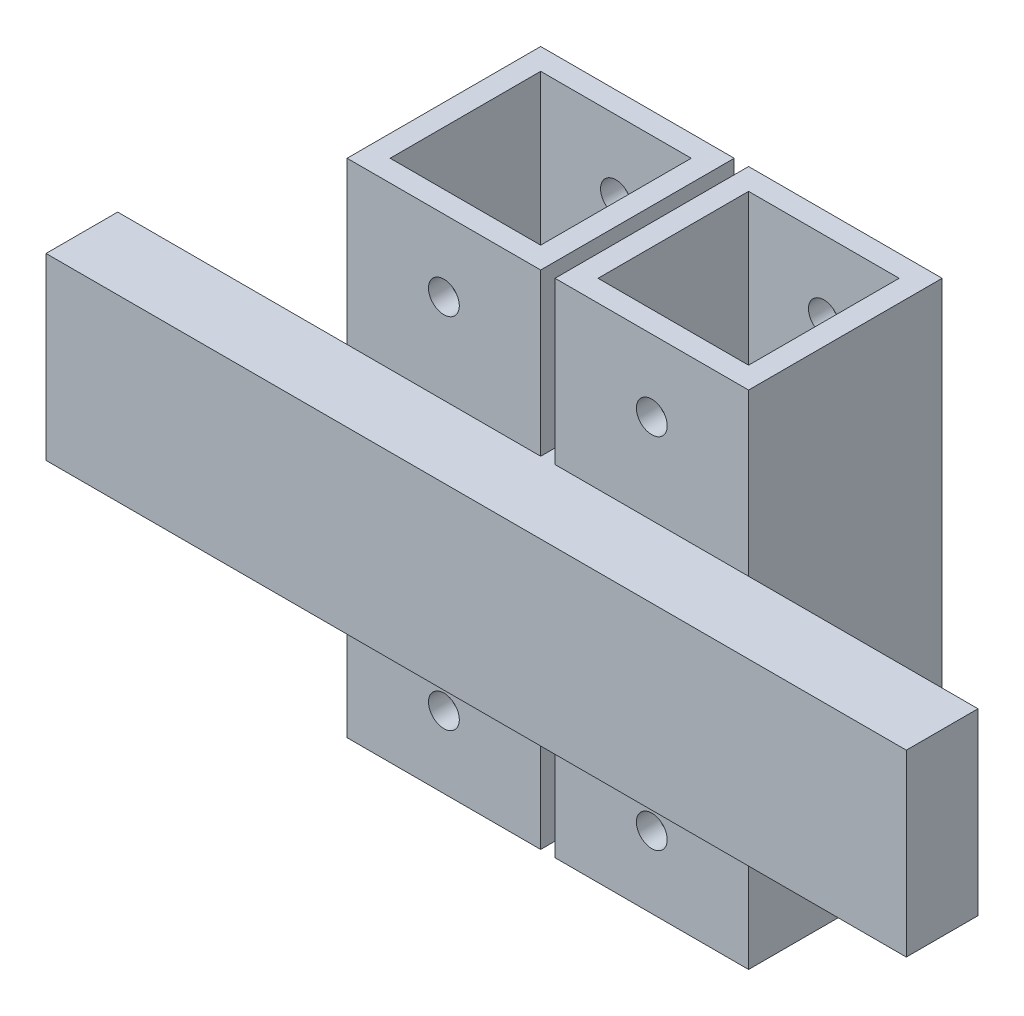
SolidWorks part; units mm, degrees
ref_plane "Front Plane" through (0, 0, 0) normal (0, 0, 1) x (1, 0, 0)
ref_plane "Top Plane" through (0, 0, 0) normal (0, 1, 0) x (1, 0, 0)
ref_plane "Right Plane" through (0, 0, 0) normal (1, 0, 0) x (0, 0, -1)
sketch "Sketch1" plane through (0, 0, 0) normal (0, 1, 0) x (1, 0, 0)
  line L1 (0, 0) -> (27, 0)
  line L2 (0, 0) -> (0, 27)
  line L3 (0, 27) -> (27, 27)
  line L4 (27, 0) -> (27, 27)
  line L5 (3, 24) -> (24, 24)
  line L6 (3, 24) -> (3, 3)
  line L7 (3, 3) -> (24, 3)
  line L8 (24, 24) -> (24, 3)
  line L9 (-29, 27) -> (-2, 27)
  line L10 (-29, 27) -> (-29, 0)
  line L11 (-29, 0) -> (-2, 0)
  line L12 (-2, 27) -> (-2, 0)
  line L13 (-5, 24) -> (-26, 24)
  line L14 (-5, 24) -> (-5, 3)
  line L15 (-5, 3) -> (-26, 3)
  line L16 (-26, 24) -> (-26, 3)
  line L17 (-25.5, 23.5) -> (-5.5, 23.5) construction
  line L18 (-25.5, 23.5) -> (-25.5, 3.5) construction
  line L19 (-25.5, 3.5) -> (-5.5, 3.5) construction
  line L20 (-5.5, 23.5) -> (-5.5, 3.5) construction
  line L21 (3.5, 23.5) -> (23.5, 23.5) construction
  line L22 (3.5, 23.5) -> (3.5, 3.5) construction
  line L23 (3.5, 3.5) -> (23.5, 3.5) construction
  line L24 (23.5, 23.5) -> (23.5, 3.5) construction
  point P25 (2.5347, 20.3062)
  point P26 (-27.2369, 24.3411)
  point P27 (-25.9138, 2.1783)
  point P28 (4.096, 3.2633)
  dimension "D1" = 9
  dimension "D2" = 0.5
  dimension "D3" = 3
  dimension "D4" = 3
  dimension "D5" = 3
  dimension "D6" = 3
  dimension "D7" = 3
  dimension "D8" = 20
  dimension "D9" = 0.5
  dimension "D10" = 0.5
  dimension "D11" = 0.5
extrude "Boss-Extrude1" add sketch "Sketch1" along normal blind 70
sketch "Sketch2" plane through (0, 0, 0) normal (0, 0, 1) x (1, 0, 0)
  line L0 (-29, 70) -> (-29, 0) construction
  line L1 (-61, 47.5) -> (59, 47.5)
  line L2 (-61, 47.5) -> (-61, 22.5)
  line L3 (-61, 22.5) -> (59, 22.5)
  line L4 (59, 47.5) -> (59, 22.5)
  line L5 (-51, 42.5) -> (49, 42.5) construction
  line L6 (-51, 42.5) -> (-51, 27.5) construction
  line L7 (-51, 27.5) -> (49, 27.5) construction
  line L8 (49, 42.5) -> (49, 27.5) construction
  point P8 (-1, 27.5)
  point P9 (-1, 22.5)
  point P10 (-61, 35)
  point P11 (-51, 35)
  point P14 (-29, 35)
  dimension "D1" = 100
  dimension "D2" = 10
  dimension "D3" = 22
  dimension "D4" = 25
  dimension "D5" = 5
extrude "Boss-Extrude2" add sketch "Sketch2" along normal blind 10
sketch "Sketch3" plane through (0, 0, -27) normal (0, 0, -1) x (-1, 0, 0)
  line L1 (0, 47.5) -> (2, 47.5)
  line L2 (0, 47.5) -> (0, 22.5)
  line L3 (0, 22.5) -> (2, 22.5)
  line L4 (2, 47.5) -> (2, 22.5)
extrude "Boss-Extrude3" add sketch "Sketch3" against normal up to surface (27 mm away) up to face at (43, 35, 0)
sketch "Sketch4" plane through (0, 0, -27) normal (0, 0, -1) x (-1, 0, 0)
  line L1 (-13.5, 60) -> (15.5, 60) construction
  line L2 (-13.5, 60) -> (-13.5, 10) construction
  line L3 (-13.5, 10) -> (15.5, 10) construction
  line L4 (15.5, 60) -> (15.5, 10) construction
  line L5 (-27, 0) -> (0, 0) construction
  line L7 (2, 0) -> (29, 0) construction
  circle A0 centre (-13.5, 60) radius 2.15
  circle A1 centre (15.5, 60) radius 2.15
  circle A2 centre (-13.5, 10) radius 2.15
  circle A3 centre (15.5, 10) radius 2.15
  point P12 (0, 0)
  point P13 (-13.5, 0)
  point P14 (0, 0)
  point P15 (15.5, 0)
  dimension "D1" = 4.3
  dimension "D2" = 50
  dimension "D3" = 10
extrude "Cut-Extrude1" cut sketch "Sketch4" against normal through all
